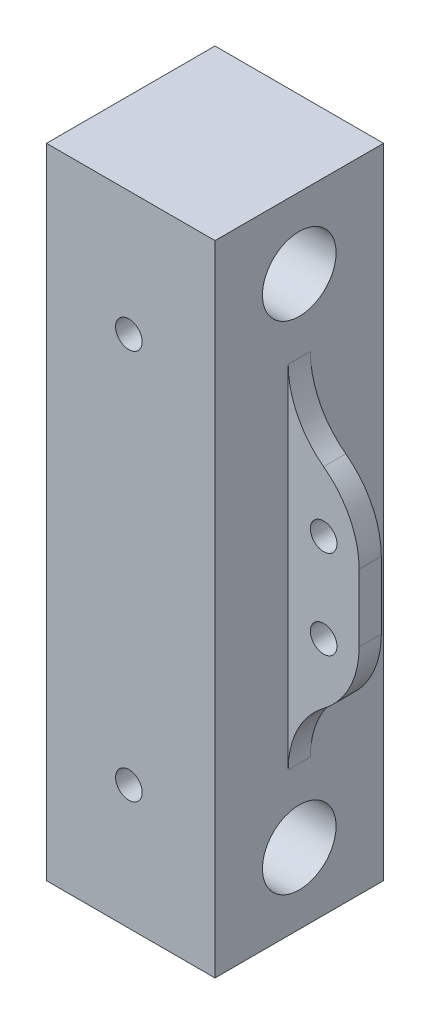
SolidWorks part; units mm, degrees
ref_plane "Front Plane" through (0, 0, 0) normal (0, 0, 1) x (1, 0, 0)
ref_plane "Top Plane" through (0, 0, 0) normal (0, 1, 0) x (1, 0, 0)
ref_plane "Right Plane" through (0, 0, 0) normal (1, 0, 0) x (0, 0, -1)
sketch "Sketch1" plane through (0, 0, 0) normal (0, 1, 0) x (1, 0, 0)
  line L1 (0, 0) -> (19, 0)
  line L2 (0, 0) -> (0, 19)
  line L3 (0, 19) -> (19, 19)
  line L4 (19, 0) -> (19, 19)
  dimension "D1" = 19
  dimension "D2" = 19
extrude "Boss-Extrude1" add sketch "Sketch1" along normal blind 72
sketch "Sketch2" plane through (19, 0, 0) normal (1, 0, 0) x (0, 0, -1)
  line L0 (19, 72) -> (19, 0) construction
  line L1 (-14.1053, 36) -> (37.2105, 36) construction
  line L2 (0, 72) -> (19, 72) construction
  circle A0 centre (9.5, 64) radius 4.15
  circle A1 centre (9.5, 8) radius 4.15
  dimension "D1" = 8.3
  dimension "D2" = 8.3
  dimension "D3" = 56
  dimension "D4" = 9.5
  dimension "D5" = 36
  dimension "D6" = 28
extrude "Cut-Extrude1" cut sketch "Sketch2" against normal through all
sketch "Sketch3" plane through (0, 0, 0) normal (0, 0, 1) x (1, 0, 0)
  line L0 (-24.3963, 36) -> (34.9222, 36) construction
  line L1 (0, 72) -> (19, 72) construction
  circle A0 centre (9.2908, 58) radius 1.5
  circle A1 centre (9.2908, 14) radius 1.5
  dimension "D1" = 3
  dimension "D2" = 36
  dimension "D3" = 22
  dimension "D4" = 22
extrude "Cut-Extrude2" cut sketch "Sketch3" against normal through all
sketch "Sketch4" plane through (19, 0, 0) normal (1, 0, 0) x (0, 0, -1)
  line L0 (9.5, 68.15) -> (9.5, 3.85) construction
  line L1 (-10.2728, 37.15) -> (49.7272, 37.15) construction
  line L2 (-10.2728, 34.85) -> (49.7272, 34.85) construction
  line L7 (-10.2728, 39.9) -> (49.7272, 39.9) construction
  line L9 (8.25, 46) -> (10.75, 46)
  line L10 (8.25, 46) -> (8.25, 26)
  line L11 (8.25, 26) -> (10.75, 26)
  line L12 (10.75, 46) -> (10.75, 26)
  line L13 (8.25, 46) -> (10.75, 26) construction
  line L14 (8.25, 26) -> (10.75, 46) construction
  circle A0 centre (9.5, 64) radius 4.15 construction
  circle A1 centre (9.5, 8) radius 4.15 construction
  point P16 (9.5, 36)
  dimension "D2" = 31
  dimension "D1" = 31
  dimension "D3" = 5.05
  dimension "D4" = 60
  dimension "D5" = 2.5
  dimension "D6" = 20
extrude "Boss-Extrude2" add sketch "Sketch4" along normal blind 8
fillet "Fillet1" radius 10 2 edges at (19, 46, -9.5) (19, 26, -9.5)
fillet "Fillet2" radius 10 2 edges at (27, 46, -9.5) (27, 26, -9.5)
sketch "Sketch5" plane through (0, 0, -10.75) normal (0, 0, -1) x (-1, 0, 0)
  line L0 (-19, 16.202) -> (-19, 55.798) construction
  line L1 (-19, 16.202) -> (-28.9734, 16.202) construction
  line L2 (-19, 55.798) -> (-28.9734, 55.798) construction
  line L3 (-28.9734, 16.202) -> (-28.9734, 55.798) construction
  line L4 (-39.6902, 36) -> (10.261, 36) construction
  line L5 (-19, 72) -> (0, 72) construction
  line L6 (-23, 48.4519) -> (-23, 32.9767) construction
  circle A1 centre (-23, 41) radius 1.5
  circle A2 centre (-23, 31) radius 1.5
  dimension "D3" = 3
  dimension "D4" = 3
  dimension "D1" = 36
  dimension "D2" = 4
  dimension "D5" = 5
  dimension "D6" = 5
extrude "Cut-Extrude3" cut sketch "Sketch5" against normal blind 10
